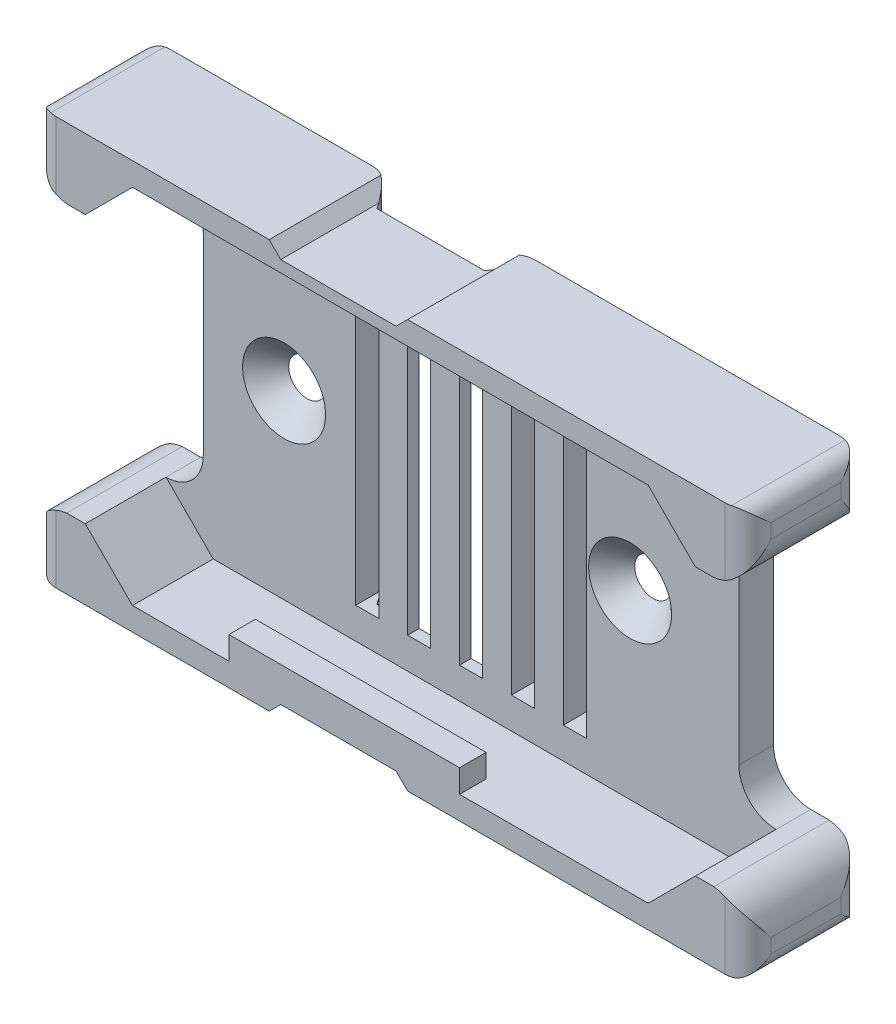
SolidWorks part; units mm, degrees
material "PET"
ref_plane "Front Plane" through (0, 0, 0) normal (0, 0, 1) x (1, 0, 0)
ref_plane "Top Plane" through (0, 0, 0) normal (0, 1, 0) x (1, 0, 0)
ref_plane "Right Plane" through (0, 0, 0) normal (1, 0, 0) x (0, 0, -1)
sketch "Sketch1" plane through (0, 0, 0) normal (0, 0, 1) x (1, 0, 0)
  line L0 (-31, 0) -> (31, 0)
  line L1 (31, 0) -> (31, 2.75)
  line L2 (28.0482, 6.094) -> (26.4482, 6.094)
  line L3 (26.4482, 6.094) -> (22.3542, 2)
  line L4 (22.3542, 2) -> (-22.3542, 2)
  line L5 (0, -3.5946) -> (0, 25.5961) construction
  line L6 (31, 17.7) -> (-31.0965, 17.7) construction
  line L7 (-26.4482, 6.094) -> (-22.3542, 2)
  line L8 (-31, 0) -> (-31, 2.75)
  line L9 (-28.0482, 6.094) -> (-26.4482, 6.094)
  line L10 (-28.0482, 29.306) -> (-26.4482, 29.306)
  line L11 (-31, 35.4) -> (-31, 32.65)
  line L12 (-26.4482, 29.306) -> (-22.3542, 33.4)
  line L13 (22.3542, 33.4) -> (-22.3542, 33.4)
  line L14 (26.4482, 29.306) -> (22.3542, 33.4)
  line L15 (28.0482, 29.306) -> (26.4482, 29.306)
  line L16 (31, 35.4) -> (31, 32.65)
  line L17 (-31, 35.4) -> (31, 35.4)
  arc A0 (31, 2.75) -> (28.0482, 6.094) centre (27.63, 2.75) ccw
  arc A1 (-31, 2.75) -> (-28.0482, 6.094) centre (-27.63, 2.75) cw
  arc A2 (-31, 32.65) -> (-28.0482, 29.306) centre (-27.63, 32.65) ccw
  arc A3 (31, 32.65) -> (28.0482, 29.306) centre (27.63, 32.65) cw
  point P18 (0, 2)
  point P19 (0, 0)
  point P25 (0, 35.4)
  point P26 (0, 33.4)
  dimension "D1" = 31
  dimension "D5" = 3.37
  dimension "D2" = 0.75
  dimension "D3" = 1.6
  dimension "D4" = 135
  dimension "D6" = 2
  dimension "D7" = 17.7
extrude "PCB Edge Guide" add sketch "Sketch1" along normal blind 7
sketch "Sketch2" plane through (0, 0, 0) normal (0, 0, -1) x (-1, 0, 0)
  line L1 (-31, 35.4) -> (31, 35.4)
  line L2 (-31, 35.4) -> (-31, 0)
  line L3 (-31, 0) -> (31, 0)
  line L4 (31, 35.4) -> (31, 0)
extrude "Rear Main Body" add sketch "Sketch2" along normal blind 3
fillet "Fillet1" radius 1.5 4 edges at (31, 0, 2) (31, 35.4, 2) (-31, 0, 2) (-31, 35.4, 2)
sketch "Sketch3" plane through (0, 2, 0) normal (0, 1, 0) x (1, 0, 0)
  line L0 (22.3542, -7) -> (-22.3542, -7) construction
  line L1 (-14, -7) -> (6, -7)
  line L2 (-14, -7) -> (-14, -4.7)
  line L3 (-14, -4.7) -> (6, -4.7)
  line L4 (6, -7) -> (6, -4.7)
  line L5 (0, 0) -> (0, -7) construction
  line L6 (22.3542, 0) -> (-22.3542, 0) construction
  dimension "D1" = 2.3
  dimension "D2" = 20
  dimension "D3" = 6
extrude "Lower PCB Fixture Tab" add sketch "Sketch3" along normal blind 2
sketch "Sketch4" plane through (0, 0, 7) normal (0, 0, 1) x (1, 0, 0)
  line L0 (0, 35.4) -> (0, 0) construction
  line L1 (29.5, 35.4) -> (-29.5, 35.4) construction
  line L2 (-31, 17.7) -> (31, 17.7) construction
  line L3 (-31, 2.75) -> (-31, 32.65) construction
  line L4 (31, 32.65) -> (31, 2.75) construction
  line L5 (-9, 0) -> (-9, 1)
  line L6 (0, 35.4) -> (-9, 35.4)
  line L7 (0, 35.4) -> (0, 34.4)
  line L8 (0, 34.4) -> (-9, 34.4)
  line L9 (-9, 35.4) -> (-9, 34.4)
  line L10 (0, 1) -> (-9, 1)
  line L11 (0, 0) -> (0, 1)
  line L12 (0, 0) -> (-9, 0)
  dimension "D1" = 1
  dimension "D2" = 9
extrude "Cable Tie Cutout" cut sketch "Sketch4" against normal through all
chamfer "Cable Tie Chamfer1" distance 1.5 angle 45 4 edges at (-9, 0, 2) (0, 0, 2) (-9, 35.4, 2) (0, 35.4, 2)
chamfer "Cable Tie Chamfer2" distance 1.5 angle 45 2 edges at (-4.5, 34.4, -3) (-4.5, 1, -3)
sketch "Sketch5" plane through (0, 0, -3) normal (0, 0, -1) x (-1, 0, 0)
  line L0 (-31, 17.7) -> (31, 17.7) construction
  line L1 (8, 30.7) -> (10, 30.7)
  line L2 (8, 30.7) -> (8, 4.7)
  line L3 (8, 4.7) -> (10, 4.7)
  line L4 (10, 30.7) -> (10, 4.7)
  line L5 (-31, 33.9) -> (-31, 1.5) construction
  line L6 (31, 1.5) -> (31, 33.9) construction
  line L7 (3.5, 30.7) -> (5.5, 30.7)
  line L8 (5.5, 30.7) -> (5.5, 4.7)
  line L9 (3.5, 30.7) -> (3.5, 4.7)
  line L10 (3.5, 4.7) -> (5.5, 4.7)
  line L11 (-1, 30.7) -> (1, 30.7)
  line L12 (1, 30.7) -> (1, 4.7)
  line L13 (-1, 30.7) -> (-1, 4.7)
  line L14 (-1, 4.7) -> (1, 4.7)
  line L15 (-5.5, 30.7) -> (-3.5, 30.7)
  line L16 (-3.5, 30.7) -> (-3.5, 4.7)
  line L17 (-5.5, 30.7) -> (-5.5, 4.7)
  line L18 (-5.5, 4.7) -> (-3.5, 4.7)
  line L19 (-10, 30.7) -> (-8, 30.7)
  line L20 (-8, 30.7) -> (-8, 4.7)
  line L21 (-10, 30.7) -> (-10, 4.7)
  line L22 (-10, 4.7) -> (-8, 4.7)
  dimension "D1" = 26
  dimension "D2" = 2
  dimension "D3" = 21
  dimension "D4" = 5
extrude "Rear Vents" cut sketch "Sketch5" against normal up to surface (3 mm away) up to face at (0, 17.7, 0)
sketch "Sketch6" plane through (0, 0, -3) normal (0, 0, -1) x (-1, 0, 0)
  line L0 (-31, 17.7) -> (31, 17.7) construction
  line L1 (-31, 33.9) -> (-31, 1.5) construction
  line L2 (31, 1.5) -> (31, 33.9) construction
  circle A0 centre (-13.79, 17.7) radius 1.6
  circle A1 centre (16.21, 17.7) radius 1.6
  dimension "D1" = 30
  dimension "D3" = 3.2
  dimension "D2" = 17.21
extrude "Cut-Extrude3" cut sketch "Sketch6" against normal up to next
chamfer "Chamfer3" distance 2 angle 45 2 edges at (-17.81, 17.7, 0) (12.19, 17.7, 0)
sketch "Sketch7" plane through (0, 0, -3) normal (0, 0, -1) x (-1, 0, 0)
  line L0 (31, 17.7) -> (-31, 17.7) construction
  line L1 (31, 1.5) -> (31, 33.9) construction
  line L2 (-31, 33.9) -> (-31, 1.5) construction
  line L3 (-8, 30.7) -> (-10, 30.7) construction
  line L4 (21.46, 4.7) -> (10.96, 4.7)
  line L5 (21.46, 4.7) -> (21.46, 30.7)
  line L6 (21.46, 30.7) -> (10.96, 30.7)
  line L7 (10.96, 4.7) -> (10.96, 30.7)
  line L8 (-8.54, 4.7) -> (-19.04, 4.7)
  line L9 (-8.54, 4.7) -> (-8.54, 30.7)
  line L10 (-8.54, 30.7) -> (-19.04, 30.7)
  line L11 (-19.04, 4.7) -> (-19.04, 30.7)
  line L12 (-10, 4.7) -> (-8, 4.7) construction
  line L13 (16.21, 35.4) -> (16.21, 0) construction
  line L14 (-13.79, 35.4) -> (-13.79, 0) construction
  line L15 (-29.5, 0) -> (-1.5, 0) construction
  point P22 (16.21, 17.7)
  point P28 (-13.79, 17.7)
  dimension "D1" = 10.5
  dimension "D2" = 10.5
extrude "Cut-Extrude4" cut sketch "Sketch7" against normal blind 1
sketch "Sketch8" plane through (0, 0, -3) normal (0, 0, -1) x (-1, 0, 0)
  line L0 (26.4482, 6.094) -> (28.0482, 6.094) construction
  line L1 (-28.0482, 6.094) -> (-26.4482, 6.094) construction
  line L2 (-26.4482, 29.306) -> (-28.0482, 29.306) construction
  line L3 (28.0482, 29.306) -> (26.4482, 29.306) construction
  line L4 (-28.0482, 6.094) -> (-26.4482, 6.094)
  line L5 (-26.4482, 29.306) -> (-28.0482, 29.306)
  line L6 (28.0482, 29.306) -> (26.4482, 29.306)
  line L7 (26.4482, 6.094) -> (28.0482, 6.094)
  line L8 (31, 2.75) -> (31.4444, 2.75)
  line L9 (31.4444, 2.75) -> (31.4444, 32.65)
  line L10 (31.4444, 32.65) -> (31, 32.65)
  line L11 (-31, 2.75) -> (-31.9815, 2.75)
  line L12 (-31.9815, 2.75) -> (-31.9815, 32.65)
  line L13 (-31.9815, 32.65) -> (-31, 32.65)
  line L14 (-31, 1.5) -> (31, 1.5) construction
  line L15 (0, -35.3244) -> (0, 38.3457) construction
  line L16 (31, 17.7) -> (-31, 17.7) construction
  line L17 (31, 1.5) -> (31, 33.9) construction
  line L18 (-31, 33.9) -> (-31, 1.5) construction
  line L19 (23.2182, 9.324) -> (23.2182, 26.076)
  line L20 (-23.2182, 9.324) -> (-23.2182, 26.076)
  arc A0 (31, 2.75) -> (28.0482, 6.094) centre (27.63, 2.75) ccw construction
  arc A1 (-28.0482, 6.094) -> (-31, 2.75) centre (-27.63, 2.75) ccw construction
  arc A2 (-31, 32.65) -> (-28.0482, 29.306) centre (-27.63, 32.65) ccw construction
  arc A3 (28.0482, 29.306) -> (31, 32.65) centre (27.63, 32.65) ccw construction
  arc A4 (-28.0482, 6.094) -> (-31, 2.75) centre (-27.63, 2.75) ccw
  arc A5 (-31, 32.65) -> (-28.0482, 29.306) centre (-27.63, 32.65) ccw
  arc A6 (28.0482, 29.306) -> (31, 32.65) centre (27.63, 32.65) ccw
  arc A7 (31, 2.75) -> (28.0482, 6.094) centre (27.63, 2.75) ccw
  arc A8 (26.4482, 6.094) -> (23.2182, 9.324) centre (26.4482, 9.324) cw
  arc A11 (26.4482, 29.306) -> (23.2182, 26.076) centre (26.4482, 26.076) ccw
  arc A12 (-26.4482, 29.306) -> (-23.2182, 26.076) centre (-26.4482, 26.076) cw
  arc A13 (-26.4482, 6.094) -> (-23.2182, 9.324) centre (-26.4482, 9.324) ccw
  point P27 (-31, 1.5)
  point P29 (0, 1.5107)
  point P30 (0, 1.5)
  point P43 (23.2182, 17.7)
  dimension "D1" = 3.23
extrude "Cut-Extrude5" cut sketch "Sketch8" against normal up to next
sketch "Sketch9" plane through (0, 0, 0) normal (0, -1, 0) x (-1, 0, 0)
  line L0 (10.5, 3) -> (9.1667, 1)
  line L1 (9.1667, 1) -> (-0.1667, 1)
  line L2 (-0.1667, 1) -> (-1.5, 3)
  line L3 (-1.5, 3) -> (10.5, 3)
  dimension "D1" = 56.31
  dimension "D2" = 56.31
  dimension "D3" = 2
extrude "Cut-Extrude6" cut sketch "Sketch9" against normal through all
sketch "Sketch10" plane through (0, 0, 0) normal (0, -1, 0) x (-1, 0, 0)
  line L0 (31, -7) -> (31, -5)
  line L1 (31, 3) -> (31, -7) construction
  line L2 (31, -7) -> (29, -7)
  line L3 (29.5, -7) -> (10.5, -7) construction
  line L4 (-29.5, -2) -> (29.5, -2) construction
  line L5 (-29.5, 3) -> (-29.5, -7) construction
  line L6 (29.5, -7) -> (29.5, 3) construction
  line L7 (0, -2) -> (0, -8.4106) construction
  line L8 (-31, -7) -> (-29, -7)
  line L9 (-31, -7) -> (-31, -5)
  line L10 (31, -7) -> (31, 3) construction
  line L13 (29.5, 3) -> (10.5, 3) construction
  line L14 (31, 1.0635) -> (31, 3)
  line L15 (31, 3) -> (29.5, 3) construction
  line L16 (31, 3) -> (29.0013, 3)
  line L17 (-31, 1.0635) -> (-31, 3)
  line L18 (-31, 3) -> (-29.0013, 3)
  arc A0 (29, -7) -> (31, -5) centre (29, -5) ccw
  arc A1 (-29, -7) -> (-31, -5) centre (-29, -5) cw
  arc A2 (31, 1.0635) -> (29.0013, 3) centre (29.001, 1) ccw
  arc A3 (-31, 1.0635) -> (-29.0013, 3) centre (-29.001, 1) cw
  dimension "D1" = 2
  dimension "D3" = 2
  dimension "D2" = 2
extrude "Cut-Extrude7" cut sketch "Sketch10" against normal through all
fillet "Fillet2" radius 2 2 edges at (-10.5, 17.7, -3) (1.5, 17.7, -3)
